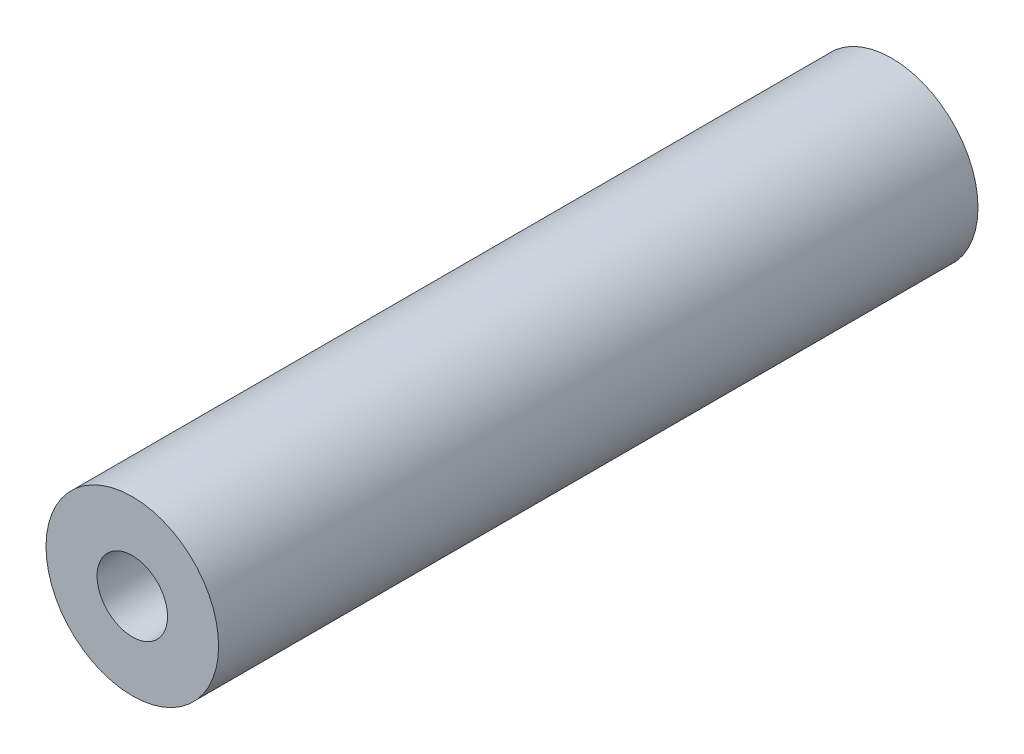
SolidWorks part; units mm, degrees
ref_plane "Front Plane" through (0, 0, 0) normal (0, 0, 1) x (1, 0, 0)
ref_plane "Top Plane" through (0, 0, 0) normal (0, 1, 0) x (1, 0, 0)
ref_plane "Right Plane" through (0, 0, 0) normal (1, 0, 0) x (0, 0, -1)
sketch "Sketch1" plane through (0, 0, 0) normal (0, 0, 1) x (1, 0, 0)
  circle A0 centre (0, 0) radius 7.9375
  circle A1 centre (0, 0) radius 3.2385
  dimension "OD" = 15.875
  dimension "ID" = 6.477
extrude "Extrude1" add sketch "Sketch1" along normal mid plane 69.85
